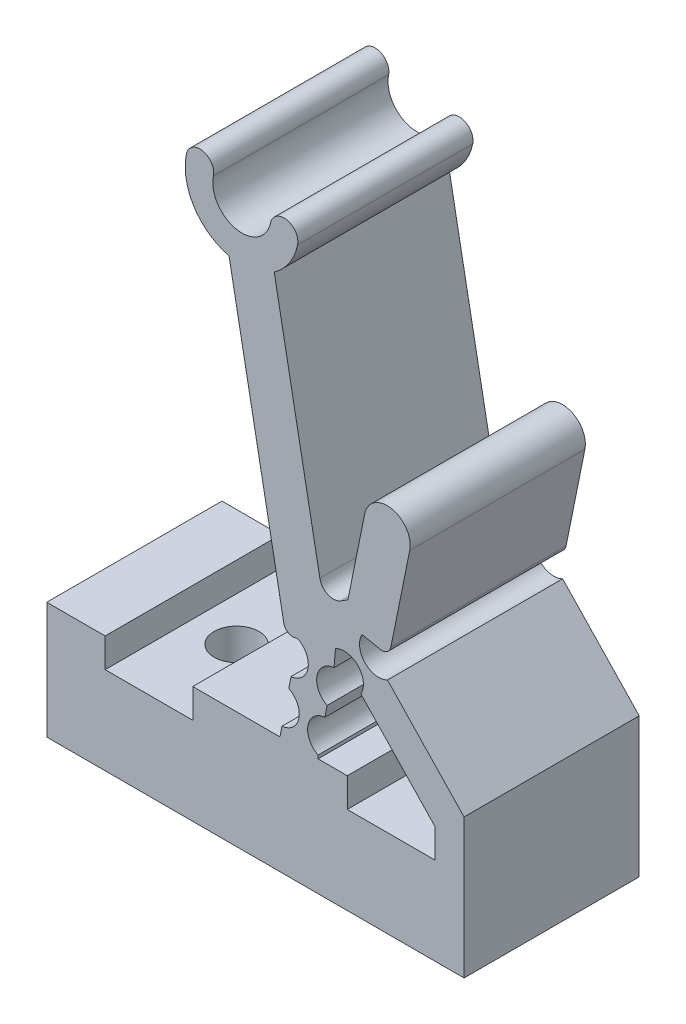
SolidWorks part; units mm, degrees
ref_plane "Front Plane" through (0, 0, 0) normal (0, 0, 1) x (1, 0, 0)
ref_plane "Top Plane" through (0, 0, 0) normal (0, 1, 0) x (1, 0, 0)
ref_plane "Right Plane" through (0, 0, 0) normal (1, 0, 0) x (0, 0, -1)
sketch "Sketch-SkeletonConfigUp" plane through (0, 0, 0) normal (0, 0, 1) x (1, 0, 0)
  line L0 (0, 0) -> (0, -50000) construction
  line L1 (0, 0) -> (7.455, 0.2734) construction
  line L2 (9.9233, 0.3639) -> (10.6101, 4.558) construction
  line L3 (10.6101, 4.558) -> (7.9471, 2.8569) construction
  line L4 (7.9471, 2.8569) -> (7.455, 0.2734) construction
  line L5 (10.6101, 4.558) -> (12.0093, 11.478) construction
  line L6 (7.9471, 2.8569) -> (4.1146, 23.199) construction
  line L7 (7.455, 0.2734) -> (9.9233, 0.3639) construction
  line L8 (-989.4051, -36.2798) -> (9.9233, 0.3639) construction
  point P12 (0, 0)
  dimension "D2" = 7.46
  dimension "D3" = 2.47
  dimension "D4" = 4.25
  dimension "D5" = 78.6
  dimension "D6" = 3.16
  dimension "D7" = 7.06
  dimension "D8" = 20.7
  dimension "D9" = 2.63
  dimension "D10" = 46
  dimension "D11" = 111.9
  dimension "D12" = 92.1
sketch "Sketch-SkeletonConfigDown" plane through (0, 0, 0) normal (0, 0, 1) x (1, 0, 0)
  line L0 (0, 0) -> (0, -50000) construction
  line L1 (0, 0) -> (7.455, 0.2734) construction
  line L2 (9.9233, 0.3639) -> (10.6101, 4.558) construction
  line L3 (10.6101, 4.558) -> (9.7761, 1.5101) construction
  line L4 (9.7761, 1.5101) -> (7.455, 0.2734) construction
  line L5 (10.6101, 4.558) -> (7.0062, 10.6288) construction
  line L6 (9.7761, 1.5101) -> (-6.7111, 14.0265) construction
  line L7 (7.455, 0.2734) -> (9.9233, 0.3639) construction
  line L8 (-993.745, -36.439) -> (9.9233, 0.3639) construction
  point P2 (0, 0)
  dimension "D2" = 7.46
  dimension "D3" = 2.47
  dimension "D4" = 4.25
  dimension "D5" = 78.6
  dimension "D6" = 3.16
  dimension "D7" = 7.06
  dimension "D8" = 20.7
  dimension "D9" = 2.63
  dimension "D10" = 46
  dimension "D11" = 111.9
  dimension "D1" = 92.1
sketch "Sketch-ConfigDown" plane through (0, 0, 0) normal (0, 0, 1) x (1, 0, 0)
  line L3 (7.5052, -0.2251) -> (4.7337, -0.3268) construction
  line L4 (9.7761, 1.5101) -> (-6.7111, 14.0265) construction
  line L6 (-200859.4238, -7365.1807) -> (9.9233, 0.3639) construction
  line L7 (7.5052, -0.2251) -> (15.9124, 0.0831) construction
  line L9 (7.455, 0.2734) -> (9.9233, 0.3639) construction
  line L10 (10.9008, 0.9001) -> (10.9374, -0.0993) construction
  line L15 (9.4668, 0.4955) -> (8.4696, -0.0359)
  line L18 (8.3945, 1.6237) -> (9.0998, 0.2999) construction
  line L19 (6.3613, 10.246) -> (8.7382, 6.242)
  line L20 (-5.5253, 12.1846) -> (7.951, 1.954)
  line L21 (8.058, 3.756) -> (-4.6183, 13.3794)
  line L22 (9.7761, 1.5101) -> (7.455, 0.2734) construction
  line L23 (2.778, 5.8811) -> (3.685, 7.0758) construction
  line L26 (10.6101, 4.558) -> (14.4503, 0.5299) construction
  line L27 (10.0779, 5.4546) -> (9.138, 2.0199) construction
  line L28 (11.1752, 5.0523) -> (15.9124, 0.0831) construction
  line L29 (14.3773, -0.4805) -> (10.5848, 3.4977) construction
  line L30 (12.8137, 1.1596) -> (13.8994, 2.1946) construction
  line L34 (4.7337, -0.3268) -> (4.7337, -3.5018) construction
  line L36 (4.7337, -3.5018) -> (15.9124, -3.5018)
  line L37 (15.9124, -3.5018) -> (15.9124, 0.0831)
  line L38 (-8.0357, 12.2817) -> (-6.0162, 14.9419) construction
  line L39 (10.6101, 4.558) -> (9.7761, 1.5101) construction
  line L40 (9.5145, 3.3957) -> (10.9613, 2.9997) construction
  line L42 (7.6511, 11.0117) -> (10.5812, 6.0759)
  line L43 (7.8883, 7.6738) -> (9.1781, 8.4395) construction
  line L44 (10.6101, 4.558) -> (7.0062, 10.6288) construction
  line L45 (7.4964, -0.3268) -> (4.7337, -0.3268) construction
  line L46 (14.3773, -0.4805) -> (15.9124, -0.4805) construction
  line L47 (12.9938, -0.3268) -> (7.4964, -0.3268)
  line L48 (8.7382, 6.242) -> (8.058, 3.756)
  line L49 (15.9124, 0.0831) -> (15.463, 0.5545)
  line L50 (10.5848, 3.4977) -> (9.5498, 4.5833) construction
  line L51 (15.463, 0.5545) -> (14.3773, -0.4805) construction
  line L52 (14.7645, 0.9249) -> (14.9455, 1.0974) construction
  line L53 (13.3423, 0.6052) -> (14.428, 1.6402) construction
  line L54 (11.1752, 5.0523) -> (10.6355, 5.6184) construction
  line L55 (10.972, 4.903) -> (11.153, 5.0755) construction
  line L56 (9.5498, 4.5833) -> (10.6355, 5.6184) construction
  line L57 (10.5848, 3.4977) -> (11.6705, 4.5327) construction
  line L58 (10.972, 4.903) -> (10.2482, 4.213) construction
  line L59 (11.6705, 4.5327) -> (14.428, 1.6402)
  line L60 (13.3423, 0.6052) -> (10.5848, 3.4977)
  line L61 (10.6355, 5.6184) -> (10.5812, 6.0759)
  line L62 (7.245, 0.6675) -> (7.1274, 0.8882) construction
  line L63 (7.1458, -0.7412) -> (6.4216, -1.127) construction
  line L64 (7.7642, 1.2879) -> (8.4696, -0.0359) construction
  line L65 (6.4404, 0.5826) -> (7.1458, -0.7412) construction
  line L66 (6.4404, 0.5826) -> (4.7337, -0.3268)
  line L67 (6.4404, 0.5826) -> (7.7642, 1.2879) construction
  line L68 (7.245, 0.6675) -> (7.665, -0.1208) construction
  line L69 (10.0853, 2.5247) -> (10.6904, 2.847) construction
  line L70 (10.7907, 1.2008) -> (11.23, 1.4349) construction
  line L71 (9.5602, 1.9151) -> (9.4427, 2.1358) construction
  line L72 (8.7615, 1.8193) -> (9.4668, 0.4955) construction
  line L73 (10.0853, 2.5247) -> (10.7907, 1.2008) construction
  line L74 (9.5602, 1.9151) -> (9.9919, 1.105) construction
  line L75 (7.7642, 1.2879) -> (8.7615, 1.8193)
  line L76 (7.951, 1.954) -> (9.2805, 2.6624)
  line L77 (9.4615, 3.9513) -> (10.971, 2.3679)
  line L78 (10.971, 2.3679) -> (11.066, 2.2683)
  line L79 (-6.7111, 14.0265) -> (-5.0362, 14.2558) construction
  line L80 (-6.7111, 14.0265) -> (-6.7111, -3.5018) construction
  line L81 (4.7337, -3.5018) -> (-6.7111, -3.5018)
  line L82 (-6.7111, -3.5018) -> (-6.7111, -0.3268)
  line L83 (-6.7111, -0.3268) -> (4.7337, -0.3268)
  line L84 (8.7615, 1.8193) -> (10.0853, 2.5247) construction
  arc A2 (-7.4311, 13.0782) -> (-5.5316, 14.188) centre (-6.7111, 14.0265) ccw
  arc A3 (-4.6183, 13.3794) -> (-4.5408, 14.3236) centre (-6.7111, 14.0265) ccw
  arc A4 (-8.0357, 12.2817) -> (-7.4311, 13.0782) centre (-7.7334, 12.68) cw
  arc A5 (-4.5408, 14.3236) -> (-5.5316, 14.188) centre (-5.0362, 14.2558) ccw
  arc A6 (-8.0357, 12.2817) -> (-5.5253, 12.1846) centre (-6.7111, 14.0265) ccw
  arc A7 (6.3613, 10.246) -> (7.6511, 11.0117) centre (7.0062, 10.6288) cw
  arc A8 (15.463, 0.5545) -> (14.428, 1.6402) centre (15.6693, 1.7874) cw
  arc A9 (14.3773, -0.4805) -> (13.3423, 0.6052) centre (13.136, -0.6277) ccw
  arc A10 (10.6355, 5.6184) -> (11.6705, 4.5327) centre (11.8768, 5.7655) ccw
  arc A11 (9.5498, 4.5833) -> (10.5848, 3.4977) centre (9.3435, 3.3505) cw
  arc A12 (7.7642, 1.2879) -> (6.4404, 0.5826) centre (6.7377, 1.6196) cw
  arc A13 (7.1458, -0.7412) -> (8.4696, -0.0359) centre (8.1723, -1.0729) cw
  arc A14 (7.1458, -0.7412) -> (7.4964, -0.3268) centre (7.8257, -0.9609) ccw
  arc A15 (8.7615, 1.8193) -> (10.0853, 2.5247) centre (9.0374, 2.8965) ccw
  arc A16 (9.4668, 0.4955) -> (10.7907, 1.2008) centre (10.5148, 0.1237) cw
  arc A19 (10.0853, 2.5247) -> (9.2805, 2.6624) centre (9.6949, 2.6632) ccw
  arc A20 (14.3773, -0.4805) -> (12.9938, -0.3268) centre (13.6677, -0.5646) cw
  arc A21 (9.5498, 4.5833) -> (9.4615, 3.9513) centre (9.4971, 4.2685) ccw
  arc A22 (10.7907, 1.2008) -> (11.066, 2.2683) centre (10.9274, 1.7348) ccw
  point P24 (8.7471, 0.9618)
  point P28 (10.9191, 0.4004)
  point P30 (8.5332, 8.0566)
  point P43 (10.2379, 3.1977)
  point P47 (14.7645, 0.9249)
  point P51 (3.2315, 6.4785)
  point P61 (13.3566, 1.6771)
  dimension "D12" = 1.5
  dimension "D3" = 2.3812
  dimension "D4" = 4.3812
  dimension "D1" = 1
  dimension "D5" = 1.5
  dimension "D6" = 7
  dimension "D2" = 3.175
  dimension "D7" = 1.5
  dimension "D9" = 1.5
  dimension "D10" = 0.25
  dimension "D8" = 1.5
  dimension "D11" = 1.5
  dimension "D13" = 0.5
  dimension "D14" = 0.5
  dimension "D15" = 45
sketch "Sketch-ConfigUp" plane through (0, 0, 0) normal (0, 0, 1) x (1, 0, 0)
  line L1 (6.7776, 2.0617) -> (6.6598, 1.4428)
  line L4 (7.9471, 2.8569) -> (7.455, 0.2734) construction
  line L5 (10.7841, 11.7257) -> (9.8745, 7.2272)
  line L6 (7.455, 0.2734) -> (9.9233, 0.3639) construction
  line L9 (10.6101, 4.558) -> (7.9471, 2.8569) construction
  line L10 (7.1519, 4.0264) -> (6.4787, 3.8995)
  line L11 (6.7187, 1.7522) -> (8.6834, 1.378) construction
  line L12 (12.1113, 5.6751) -> (10.6439, 5.9718)
  line L16 (12.024, 4.5242) -> (10.6439, 5.9718) construction
  line L17 (13.2345, 11.2303) -> (12.1113, 5.6751)
  line L18 (10.6101, 4.558) -> (12.0093, 11.478) construction
  line L19 (10.315, 9.4057) -> (12.7654, 8.9103) construction
  line L20 (3.4089, 20.1933) -> (6.4787, 3.8995)
  line L21 (8.5546, 6.384) -> (5.8657, 20.6561)
  line L22 (7.9471, 2.8569) -> (4.1146, 23.199) construction
  line L23 (5.3299, 9.997) -> (7.7867, 10.4599) construction
  line L26 (11.3002, 3.8342) -> (14.4503, 0.5299) construction
  line L27 (-200855.0838, -7365.0216) -> (9.9233, 0.3639) construction
  line L30 (12.336, 1.2984) -> (13.7836, 2.6784) construction
  line L38 (2.5546, 22.9051) -> (4.1146, 23.199) construction
  line L39 (4.1146, 23.199) -> (7.1366, 22.5661) construction
  line L42 (9.8377, -1.0766) -> (9.8377, -7.4266) construction
  line L43 (9.1963, 4.5918) -> (10.6439, 5.9718) construction
  line L44 (7.6421, 1.2557) -> (7.2679, -0.709) construction
  line L46 (8.6244, 1.0686) -> (8.2502, -0.8961) construction
  line L47 (10.5764, 3.1442) -> (12.024, 4.5242) construction
  line L48 (16.1877, 0.1566) -> (12.024, 4.5242)
  line L51 (7.7015, 2.9037) -> (8.1927, 2.8101) construction
  line L52 (6.7776, 2.0617) -> (8.7423, 1.6875) construction
  line L53 (7.1519, 4.0264) -> (9.1165, 3.6521) construction
  line L54 (14.6002, -1.0766) -> (14.6002, -7.4266) construction
  line L56 (7.76, 1.8746) -> (8.1342, 3.8393) construction
  line L59 (7.1519, 4.0264) -> (6.7776, 2.0617) construction
  line L61 (8.7423, 1.6875) -> (8.6244, 1.0686)
  line L62 (6.6598, 1.4428) -> (8.6244, 1.0686) construction
  line L67 (4.1146, 23.199) -> (1.0927, 23.832) construction
  line L69 (10.7911, 4.7305) -> (10.4292, 4.3855) construction
  line L71 (10.6439, 5.9718) -> (9.6089, 7.0575) construction
  line L73 (6.6598, 1.4428) -> (6.2855, -0.5219) construction
  line L77 (14.4503, 0.5299) -> (9.9233, 0.3639) construction
  line L78 (9.1963, 4.5918) -> (9.1165, 3.6521)
  line L79 (8.5546, 6.384) -> (9.8745, 7.2272)
  line L81 (11.3002, 3.8342) -> (9.9201, 5.2818) construction
  line L82 (10.315, 9.4057) -> (9.8745, 7.2272) construction
  line L92 (9.8377, -1.0766) -> (14.6002, -1.0766)
  line L93 (7.2094, 0.3201) -> (7.7006, 0.2266) construction
  line L94 (16.1877, -7.4266) -> (16.1877, 0.1566)
  line L107 (6.1799, -1.0766) -> (-6.5007, -1.0766)
  line L108 (-6.5007, -1.0766) -> (-6.5007, -7.4266)
  line L109 (-6.5007, -7.4266) -> (16.1877, -7.4266)
  line L115 (6.2855, -0.5219) -> (6.1799, -1.0766)
  line L116 (12.8073, 0.8041) -> (10.5764, 3.1442)
  line L117 (10.5764, 3.1442) -> (9.1963, 4.5918) construction
  line L121 (9.1165, 3.6521) -> (8.7423, 1.6875) construction
  line L125 (8.2502, -0.8961) -> (8.2502, -1.0766)
  line L126 (12.8073, 0.8041) -> (14.6002, -1.0766)
  line L128 (8.5546, 6.384) -> (9.0675, 3.6615) construction
  line L129 (6.2855, -0.5219) -> (8.2502, -0.8961) construction
  line L130 (8.2502, -1.0766) -> (9.8377, -1.0766)
  line L131 (14.6002, -1.0766) -> (16.1877, -1.0766) construction
  arc A0 (10.7841, 11.7257) -> (13.2345, 11.2303) centre (12.0093, 11.478) cw
  arc A2 (2.5609, 23.5245) -> (5.6684, 22.8736) centre (4.1146, 23.199) ccw
  arc A3 (5.8657, 20.6561) -> (7.1366, 22.5661) centre (4.1146, 23.199) ccw
  arc A4 (1.0927, 23.832) -> (2.5609, 23.5245) centre (1.8268, 23.6783) cw
  arc A5 (7.1366, 22.5661) -> (5.6684, 22.8736) centre (6.4025, 22.7198) ccw
  arc A6 (1.0927, 23.832) -> (3.4089, 20.1933) centre (4.1146, 23.199) ccw
  arc A7 (8.7423, 1.6875) -> (9.1165, 3.6521) centre (9.2159, 2.6152) cw
  arc A15 (8.6244, 1.0686) -> (8.2502, -0.8961) centre (8.7238, 0.0317) ccw
  arc A21 (6.7776, 2.0617) -> (7.1519, 4.0264) centre (6.6782, 3.0986) ccw
  arc A42 (6.6598, 1.4428) -> (6.2855, -0.5219) centre (6.1861, 0.515) cw
  arc A43 (12.024, 4.5242) -> (10.6439, 5.9718) centre (11.545, 5.4493) cw
  arc A44 (10.5764, 3.1442) -> (9.1963, 4.5918) centre (9.6752, 3.6667) ccw
  point P27 (7.701, 1.5651)
  point P38 (11.5402, 9.158)
  point P51 (6.5583, 10.2285)
  point P61 (13.0598, 1.9884)
  point P125 (7.7006, 0.2266)
  point P130 (7.2094, 0.3201)
  dimension "D3" = 3.175
  dimension "D4" = 6.175
  dimension "D5" = 7
  dimension "D14" = 22.5
  dimension "D21" = 22.5
  dimension "D22" = 2
  dimension "D24" = 0.5
  dimension "D8" = 4.7625
  dimension "D9" = 2
  dimension "D10" = 2
  dimension "D11" = 0.5
  dimension "D6" = 2
  dimension "D7" = 0.5
  dimension "D12" = 1.5
  dimension "D16" = 2.5
  dimension "D13" = 1.5875
  dimension "D15" = 6.35
extrude "Boss-ConfigUp" add sketch "Sketch-ConfigUp" along normal blind 9.525
sketch "Sketch2" plane through (0.0043, -1.0766, 0) normal (0, -1, 0) x (-1, 0, 0)
  line L0 (6.505, -9.525) -> (-16.1834, -9.525) construction
  line L1 (-14.5959, 0) -> (-9.8334, 0)
  line L2 (-14.5959, 0) -> (-14.5959, -9.525)
  line L3 (-14.5959, -9.525) -> (-9.8334, -9.525)
  line L4 (-9.8334, 0) -> (-9.8334, -9.525)
  line L12 (-14.5959, 0) -> (-9.8334, -9.525) construction
  line L17 (-14.5959, -9.525) -> (-9.8334, 0) construction
  line L18 (6.505, 0) -> (-16.1834, 0) construction
  line L19 (6.505, -9.525) -> (6.505, 0) construction
  line L20 (3.33, -9.525) -> (3.33, 0)
  line L21 (3.33, -9.525) -> (-1.4325, -9.525)
  line L22 (3.33, 0) -> (-1.4325, 0)
  line L23 (-1.4325, -9.525) -> (-1.4325, 0)
  line L24 (3.33, -9.525) -> (-1.4325, 0) construction
  line L25 (3.33, 0) -> (-1.4325, -9.525) construction
  line L26 (6.505, -9.525) -> (-16.1834, -9.525) construction
  point P4 (-12.2147, -4.7625)
  point P26 (0.9487, -4.7625)
  dimension "D1" = 4.7625
  dimension "D2" = 3.175
extrude "Cut-NutSlot" cut sketch "Sketch2" along normal blind 1.5875
hole_wizard "#2 Clearance Hole1" positions "Sketch4" profile "Sketch3" hole size "#2" standard "ANSI Inch" end condition up to next
sketch "Sketch4" plane through (0, -7.4266, 0) normal (0, -1, 0) x (-1, 0, 0)
  line L16 (-14.6002, 0) -> (-9.8377, -9.525) construction
  point P40 (-12.219, -4.7625)
  point P44 (0.9444, -4.7625)
sketch "Sketch3" plane through (12.219, -7.4266, 4.7625) normal (1, 0, 0) x (0, 0, -1)
  line L0 (0, 0) -> (0, 4.7625)
  line L1 (0, 4.7625) -> (1.2192, 4.7625)
  line L2 (1.2192, 4.7625) -> (1.2192, 0)
  line L5 (1.2192, 0) -> (0, 0)
  line L11 (0, -6.35) -> (0, 107.95) construction
  dimension "Thru Hole Dia." = 2.4384
  dimension "Thru Hole Depth" = 4.7625
ref_plane "Plane-Midplane" through (0, 0, 4.7625) normal (0, 0, -1) x (-1, 0, 0)
fillet "Fillet1" radius 0.5 2 edges at (12.1113, 5.6751, 4.7625) (6.4787, 3.8995, 4.7625)
fillet "Fillet2" radius 0.75 1 edges at (8.5546, 6.384, 4.7625)
ref_axis "Axis-CableUp" through (4.1146, 23.199, 9.525) along (0, 0, -1)
ref_axis "Axis-CableDown" through (-6.7111, 14.0265, 0) along (0, 0, 1)
sketch "Sketch5" plane through (0, 0, 0) normal (0, 0, 1) x (1, 0, 0)
  point P0 (-6.7111, 14.0265)
  point P2 (4.1146, 23.199)
  dimension "D1" = 9.1725
  dimension "D2" = 10.8258
equation "\"axle-diameter\"=2"
equation "\"switch-thickness\"=12"
equation "\"base-width\"=4.0"
equation "\"axle-bushing-radius\"=3"
equation "\"clearance\"= 0.25"
equation "\"arm-width\"=1.5"
equation "\"min-diameter\"=70"
equation "\"alpha\"=92.1"
equation "\"beta\"=26.0"
equation "\"gamma\"=78.6"
equation "\"delta\"=111.9"
equation "\"epsilon\"=46.0"
equation "\"eta\"=-228.1"
equation "\"l_AB\"=2.47"
equation "\"l_AC\"=2.63"
equation "\"l_BD\"=4.25"
equation "\"l_CD\"=3.16"
equation "\"l_CE\"=20.70"
equation "\"l_DF\"=7.06"
equation "\"l_OA\"=7.46"
equation "\"D2@Sketch-SkeletonConfigUp\" = \"l_OA\""
equation "\"D3@Sketch-SkeletonConfigUp\" = \"l_AB\""
equation "\"D4@Sketch-SkeletonConfigUp\" = \"l_BD\""
equation "\"D5@Sketch-SkeletonConfigUp\" = \"gamma\""
equation "\"D6@Sketch-SkeletonConfigUp\" = \"l_CD\""
equation "\"D7@Sketch-SkeletonConfigUp\" = \"l_DF\""
equation "\"D8@Sketch-SkeletonConfigUp\" = \"l_CE\""
equation "\"D9@Sketch-SkeletonConfigUp\" = \"l_AC\""
equation "\"D_groove\"=3.175"
equation "\"D3@Sketch-ConfigUp\" = \"D_groove\""
equation "\"D4@Sketch-ConfigUp\" = \"D_groove\" + 2 * \"arm-width\""
equation "\"D7@Sketch-SkeletonConfigDown\" = \"l_DF\""
equation "\"D6@Sketch-SkeletonConfigDown\" = \"l_CD\""
equation "\"D2@Sketch-SkeletonConfigDown\" = \"l_OA\""
equation "\"D3@Sketch-SkeletonConfigDown\" = \"l_AB\""
equation "\"D9@Sketch-SkeletonConfigDown\" = \"l_AC\""
equation "\"D8@Sketch-SkeletonConfigDown\" = \"l_CE\""
equation "\"D5@Sketch-SkeletonConfigDown\" = \"gamma\""
equation "\"D4@Sketch-SkeletonConfigDown\" = \"l_BD\""
equation "\"D1@Sketch-SkeletonConfigDown\" = \"alpha\""
equation "\"D5@Sketch-ConfigDown\" = \"arm-width\""
equation "\"hinge_length\"=1.5"
equation "\"hinge_depth\"=0.25"
equation "\"D9@Sketch-ConfigDown\" = \"hinge_length\""
equation "\"D10@Sketch-ConfigDown\" = \"hinge_depth\""
equation "\"D8@Sketch-ConfigDown\" = \"hinge_length\""
equation "\"D11@Sketch-ConfigDown\" = \"hinge_length\""
equation "\"D12@Sketch-ConfigDown\" = \"hinge_length\""
equation "\"D10@Sketch-SkeletonConfigUp\"=\"epsilon\""
equation "\"D11@Sketch-SkeletonConfigUp\"=\"delta\""
equation "\"D12@Sketch-SkeletonConfigUp\"=\"alpha\""
equation "\"D11@Sketch-SkeletonConfigDown\"=\"delta\""
equation "\"D10@Sketch-SkeletonConfigDown\"=\"epsilon\""
